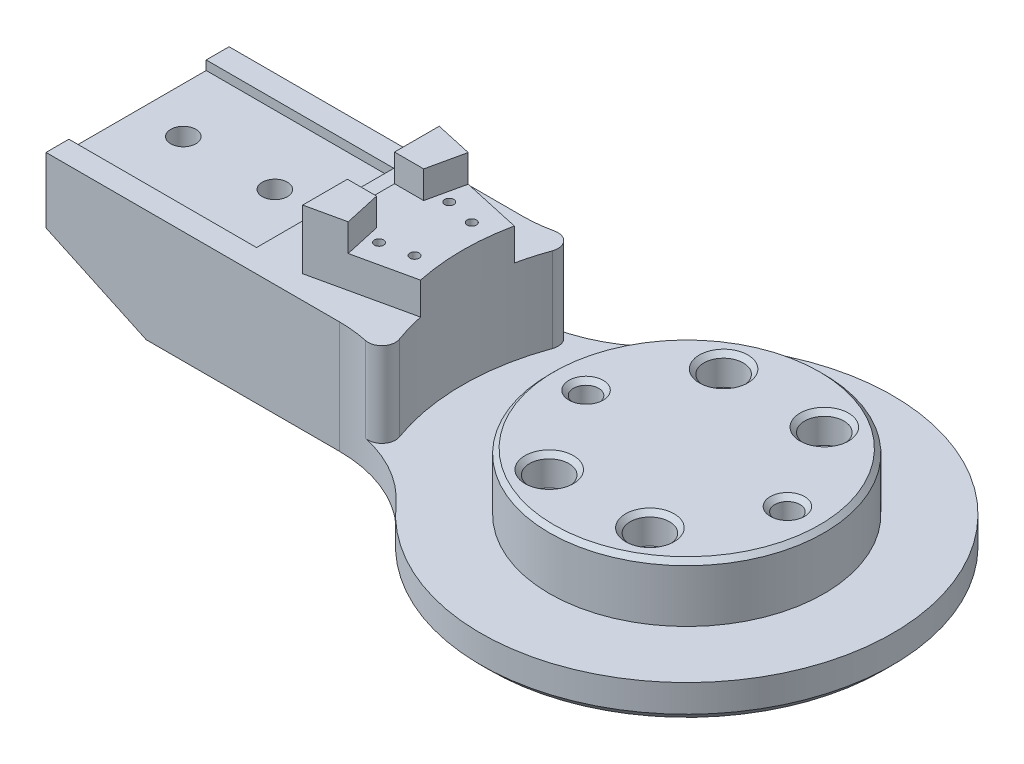
SolidWorks part; units mm, degrees
ref_plane "Front Plane" through (0, 0, 0) normal (0, 0, 1) x (1, 0, 0)
ref_plane "Top Plane" through (0, 0, 0) normal (0, 1, 0) x (1, 0, 0)
ref_plane "Right Plane" through (0, 0, 0) normal (1, 0, 0) x (0, 0, -1)
sketch "Sketch1" plane through (0, 0, 0) normal (0, 1, 0) x (1, 0, 0)
  circle A0 centre (0, 0) radius 30
  dimension "D1" = 60
extrude "Boss-Extrude1" add sketch "Sketch1" along normal blind 12.5
sketch "Sketch3" plane through (0, 0, 0) normal (0, -1, 0) x (1, 0, 0)
  line L1 (-28.2, -28.2) -> (28.2, -28.2) construction
  line L2 (-28.2, -28.2) -> (-28.2, 28.2) construction
  line L3 (-28.2, 28.2) -> (28.2, 28.2) construction
  line L4 (28.2, -28.2) -> (28.2, 28.2) construction
  line L5 (-28.2, -28.2) -> (28.2, 28.2) construction
  line L6 (-28.2, 28.2) -> (28.2, -28.2) construction
  circle A0 centre (0, 0) radius 45
  point P0 (0, 0)
  dimension "D2" = 90
  dimension "D1" = 56.4
extrude "Boss-Extrude3" add sketch "Sketch3" along normal blind 8
sketch "Sketch17" plane through (0, 12.5, 0) normal (0, 1, 0) x (1, 0, 0)
  circle A0 centre (0, 0) radius 22 construction
  circle A6 centre (22, 0) radius 2.75
  circle A12 centre (-22, 0) radius 2.75
  dimension "D3" = 5.5
  dimension "D1" = 44
extrude "Cut-Extrude9" cut sketch "Sketch17" against normal blind 6 contours A6 | A12 region at (22, 12.5, 0) region at (-22, 12.5, 0)
sketch "Sketch19" plane through (0, 12.5, 0) normal (0, 1, 0) x (1, 0, 0)
  circle A0 centre (-11, -19.0526) radius 4.3
  circle A1 centre (11, -19.0526) radius 4.3
  circle A2 centre (11, 19.0526) radius 4.3
  circle A3 centre (-11, 19.0526) radius 4.3
  circle A4 centre (0, 0) radius 22 construction
  dimension "D1" = 8.6
  dimension "D2" = 44
extrude "Cut-Extrude12" cut sketch "Sketch19" against normal blind 6.5
sketch "Sketch22" plane through (0, -8, 0) normal (0, -1, 0) x (1, 0, 0)
  line L0 (-45, 0) -> (-120, 0) construction
  line L1 (-40.3113, 20) -> (-120, 20)
  line L2 (-40.3113, -20) -> (-120, -20)
  line L4 (-120, 20) -> (-120, -20)
  line L5 (-1.6087, 20) -> (-95.5859, 20) construction
  line L6 (-1.6087, 0) -> (-95.5859, 0) construction
  line L7 (-1.6087, -20) -> (-95.5859, -20) construction
  circle A0 centre (0, 0) radius 45 construction
  arc A1 (-40.3113, 20) -> (-40.3113, -20) centre (0, 0) ccw
  dimension "D3" = 120
  dimension "D1" = 20
  dimension "D2" = 20
extrude "Boss-Extrude5" add sketch "Sketch22" against normal up to surface (8 mm away) up to face at (0, 0, 30)
sketch "Sketch24" plane through (0, 0, 0) normal (0, 1, 0) x (1, 0, 0)
  line L3 (-120, -20) -> (-44.7325, -20)
  line L4 (-120, 20) -> (-120, -20)
  line L5 (-44.7325, 20) -> (-120, 20)
  line L6 (0, 0) -> (-127.3918, 0) construction
  arc A0 (-44.7325, 20) -> (-44.7325, -20) centre (0, 0) ccw
  dimension "D1" = 98
  dimension "D2" = 40
  dimension "D3" = 120
extrude "Boss-Extrude6" add sketch "Sketch24" along normal blind 18.5
fillet "Fillet1" radius 30 2 edges at (-40.3113, -4, -20) (-40.3113, -4, 20)
sketch "Sketch25" plane through (-120, 0, 0) normal (-1, 0, 0) x (0, 0, 1)
  line L0 (-20, 18.5) -> (20, 18.5) construction
  line L1 (-15, 20.5) -> (15, 20.5)
  line L2 (-15, 20.5) -> (-15, 16.5)
  line L3 (-15, 16.5) -> (15, 16.5)
  line L4 (15, 20.5) -> (15, 16.5)
  line L5 (-15, 20.5) -> (15, 16.5) construction
  line L6 (-15, 16.5) -> (15, 20.5) construction
  point P0 (0, 18.5)
  dimension "D1" = 4
  dimension "D2" = 30
extrude "Cut-Extrude14" cut sketch "Sketch25" against normal blind 41
sketch "Sketch26" plane through (0, -8, 0) normal (0, -1, 0) x (1, 0, 0)
  line L0 (-110.0843, 0) -> (-45.9178, 0) construction
  line L3 (-120, 20) -> (-120, -20) construction
  circle A0 centre (-110, 0) radius 2.75
  circle A1 centre (-90, 0) radius 2.75
  dimension "D3" = 5.5
  dimension "D1" = 10
  dimension "D2" = 20
extrude "Cut-Extrude15" cut sketch "Sketch26" against normal through all
sketch "Sketch27" plane through (0, -8, 0) normal (0, -1, 0) x (1, 0, 0)
  line L1 (-94.7333, -0.0935) -> (-92.2857, -4.146)
  line L2 (-92.2857, -4.146) -> (-87.5524, -4.0524)
  line L3 (-87.5524, -4.0524) -> (-85.2667, 0.0935)
  line L4 (-85.2667, 0.0935) -> (-87.7143, 4.146)
  line L5 (-87.7143, 4.146) -> (-92.4476, 4.0524)
  line L6 (-92.4476, 4.0524) -> (-94.7333, -0.0935)
  line L7 (-114.7333, -0.0935) -> (-112.2857, -4.146)
  line L8 (-112.2857, -4.146) -> (-107.5524, -4.0524)
  line L9 (-107.5524, -4.0524) -> (-105.2667, 0.0935)
  line L10 (-105.2667, 0.0935) -> (-107.7143, 4.146)
  line L11 (-107.7143, 4.146) -> (-112.4476, 4.0524)
  line L12 (-112.4476, 4.0524) -> (-114.7333, -0.0935)
  circle A0 centre (-90, 0) radius 4.1 construction
  circle A1 centre (-110, 0) radius 4.1 construction
  dimension "D1" = 8.2
extrude "Cut-Extrude16" cut sketch "Sketch27" against normal blind 12
sketch "Sketch30" plane through (0, -8, 0) normal (0, -1, 0) x (1, 0, 0)
  line L0 (0, 0) -> (143.771, 0) construction
sketch "Sketch31" plane through (0, 18.5, 0) normal (0, 1, 0) x (1, 0, 0)
  line L0 (-49, 0) -> (-69, 0) construction
  line L2 (-47.9175, -10.2428) -> (-69, -14.9167)
  line L7 (-79, -15) -> (-120, -15)
  line L8 (-120, -15) -> (-120, -20)
  line L9 (-120, -20) -> (-55.9017, -20)
  line L10 (-55.9017, 20) -> (-120, 20)
  line L11 (-120, 20) -> (-120, 15)
  line L12 (-120, 15) -> (-79, 15)
  line L13 (-79, 15) -> (-79, -15)
  line L15 (-120, -15) -> (-120, -20)
  line L23 (-69, -14.9167) -> (-69, 14.9167)
  line L24 (-47.9175, 10.2428) -> (-69, 14.9167)
  arc A3 (-43.4126, -22.7232) -> (-55.9017, -20) centre (-55.9017, -50) ccw
  arc A4 (-43.4126, 22.7232) -> (-43.4126, -22.7232) centre (0, 0) ccw
  arc A5 (-43.4126, -22.7232) -> (-55.9017, -20) centre (-55.9017, -50) ccw
  arc A7 (-47.9175, 10.2428) -> (-47.9175, -10.2428) centre (0, 0) ccw
  arc A9 (-55.9017, 20) -> (-43.4126, 22.7232) centre (-55.9017, 50) ccw
  arc A10 (-55.9017, 20) -> (-43.4126, 22.7232) centre (-55.9017, 50) ccw
  point P13 (-52.3713, 0)
  point P25 (-69, 0)
  arc M18 (-43.4126, -22.7232) -> (-43.4126, 22.7232) centre (0, 0) cw
  dimension "D2" = 20
  dimension "D3" = 25
  dimension "D1" = 0
extrude "Boss-Extrude7" add sketch "Sketch31" along normal blind 13 contours L0 A7 L24 L23 | L0 L23 L2 M18 region at (-59.4207, 18.5, 6.4345) region at (-59.4207, 18.5, -6.4345)
sketch "Sketch33" plane through (0, 31.5, 0) normal (0, 1, 0) x (1, 0, 0)
  line L0 (-47.8722, -10.2328) -> (-60.8569, -13.1115)
  line L1 (-47.9175, -10.2428) -> (-69, -14.9167) construction
  line L2 (-47.9175, -10.2428) -> (-69, -14.9167) construction
  line L3 (-60.8569, -13.1115) -> (-62.6228, -5.1463)
  line L5 (-49.4834, -2.9651) -> (-47.8722, -10.2328)
  line L6 (-48.9387, 0) -> (-52.4764, 0) construction
  line L8 (-49.4834, 2.9651) -> (-47.8722, 10.2328)
  line L9 (-47.8722, 10.2328) -> (-60.8569, 13.1115)
  line L10 (-60.8569, 13.1115) -> (-62.6228, 5.1463)
  line L12 (-49.4834, -2.9651) -> (-49.4834, 2.9651)
  line L13 (-62.6228, -5.1463) -> (-69, -5.1463)
  line L14 (-69, -14.9167) -> (-69, 14.9167) construction
  line L15 (-62.6228, 5.1463) -> (-69, 5.1463)
  line L16 (-69, -5.1463) -> (-69, 5.1463)
  line L17 (-47.9175, 10.2428) -> (-69, 14.9167) construction
  dimension "D1" = 13.3
extrude "Cut-Extrude21" cut sketch "Sketch33" against normal blind 6 contours L10 L15 L16 L13 L3 L0 L5 L12 L8 L9
sketch "Sketch34" plane through (0, 25.5, 0) normal (0, 1, 0) x (1, 0, 0)
  line L0 (-54.3872, 11.6771) -> (-56.4752, 2.2587) construction
  line L1 (-47.9175, 10.2428) -> (-60.8569, 13.1115) construction
  line L2 (-49.4834, 0) -> (-79, 0) construction
  line L3 (-49.4834, -2.9651) -> (-49.4834, 2.9651) construction
  line L4 (-79, 15) -> (-79, -15) construction
  line L5 (-62.2638, 6.7655) -> (-49.279, 3.8869) construction
  line L6 (-60.8569, 13.1115) -> (-62.6228, 5.1463) construction
  line L7 (-49.4834, 2.9651) -> (-48.2601, 8.483) construction
  line L8 (-60.8569, 13.1115) -> (-62.6228, 5.1463) construction
  line L9 (-61.9608, 8.1323) -> (-48.976, 5.2537) construction
  line L10 (-58.967, 6.0347) -> (-57.4552, 12.8538) construction
  circle A0 centre (-53.2191, -6.2566) radius 1
  circle A1 centre (-59.5633, -7.6712) radius 1
  circle A2 centre (-59.5633, 7.6712) radius 1
  circle A4 centre (-53.2191, 6.2566) radius 1
  dimension "D1" = 6.5
  dimension "D3" = 3.25
  dimension "D2" = 1.4
extrude "Cut-Extrude22" cut sketch "Sketch34" against normal blind 5
chamfer "Chamfer4" distance 1 angle 45 1 edges at (0, 12.5, 30)
chamfer "Chamfer5" distance 1 angle 45 6 edges at (-11, 12.5, -14.7526) (-11, 12.5, 23.3526) (11, 12.5, 23.3526) (22, 12.5, 2.75) (11, 12.5, -14.7526) (-22, 12.5, 2.75)
sketch "Sketch35" plane through (0, -8, 0) normal (0, -1, 0) x (1, 0, 0)
  circle A0 centre (-22, 0) radius 4.6
  circle A1 centre (22, 0) radius 4.6
  dimension "D1" = 9.2
extrude "Cut-Extrude23" cut sketch "Sketch35" against normal blind 15
fillet "Fillet3" radius 3 2 edges at (-43.4126, 9.25, -22.7232) (-43.4126, 9.25, 22.7232)
chamfer "Chamfer6" distance 10 angle 65 1 edges at (-120, -8, 0) first distance on face at (-120, 11.375, 0)
chamfer "Chamfer7" distance 2 angle 45 7 edges at (-109.2775, -3, 20) (-77.2283, -8, 20) (-43.6543, -8, 22.6139) (45, -8, 0) (-43.6543, -8, -22.6139) (-77.2283, -8, -20) (-109.2775, -3, -20)
chamfer "Chamfer8" distance 1 angle 45 2 edges at (-22, -8, -4.6) (22, -8, -4.6)
sketch "Sketch37" plane through (0, 25.5, 0) normal (0, 1, 0) x (1, 0, 0)
  line L1 (-55.4174, -14.5064) -> (-42.5826, -14.5064)
  line L2 (-55.4174, -14.5064) -> (-55.4174, 14.5064)
  line L3 (-55.4174, 14.5064) -> (-42.5826, 14.5064)
  line L4 (-42.5826, -14.5064) -> (-42.5826, 14.5064)
  line L5 (-55.4174, -14.5064) -> (-42.5826, 14.5064) construction
  line L6 (-55.4174, 14.5064) -> (-42.5826, -14.5064) construction
  arc A0 (-46.0546, 16.7325) -> (-46.0546, -16.7325) centre (0, 0) ccw construction
  point P0 (-49, 0)
extrude "Cut-Extrude24" cut sketch "Sketch37" along normal blind 15
